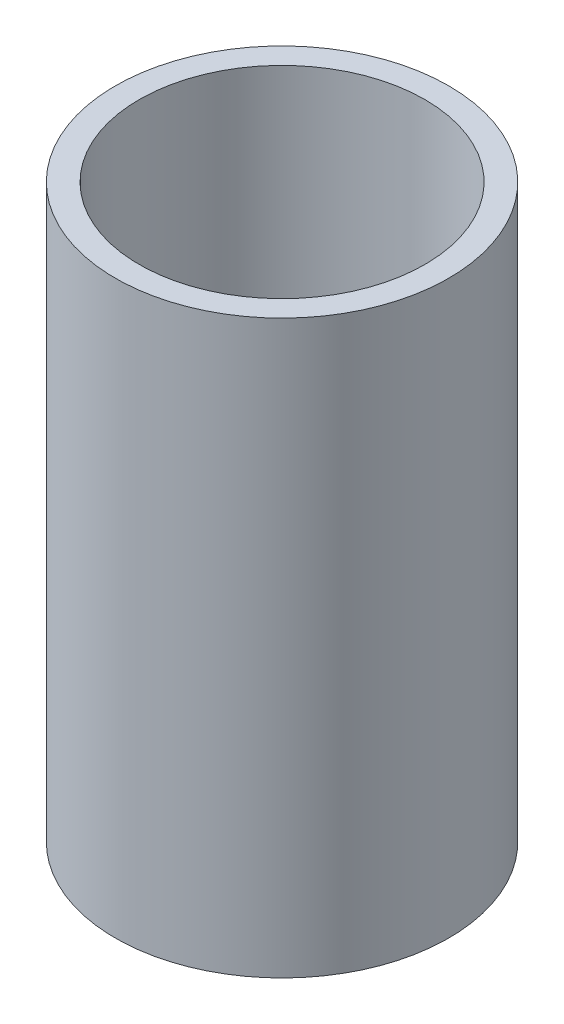
SolidWorks part; units mm, degrees
material "Acrylic (Medium-high impact)"
ref_plane "Front Plane" through (0, 0, 0) normal (0, 0, 1) x (1, 0, 0)
ref_plane "Top Plane" through (0, 0, 0) normal (0, 1, 0) x (1, 0, 0)
ref_plane "Right Plane" through (0, 0, 0) normal (1, 0, 0) x (0, 0, -1)
sketch "Sketch1" plane through (0, 0, 0) normal (0, 1, 0) x (1, 0, 0)
  circle A0 centre (0, 0) radius 22.225
  circle A1 centre (0, 0) radius 19.05
  dimension "D1" = 44.45
  dimension "D2" = 3.175
extrude "Boss-Extrude1" add sketch "Sketch1" along normal blind 76.2
